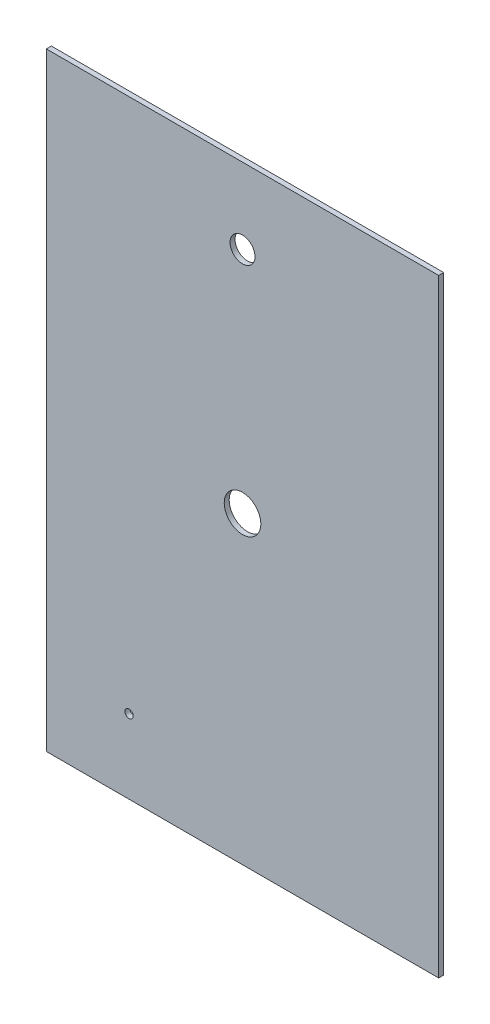
SolidWorks part; units mm, degrees
ref_plane "Alzado" through (0, 0, 0) normal (0, 0, 1) x (1, 0, 0)
ref_plane "Planta" through (0, 0, 0) normal (0, 1, 0) x (1, 0, 0)
ref_plane "Vista lateral" through (0, 0, 0) normal (1, 0, 0) x (0, 0, -1)
sketch "Sketch1" plane through (0, 0, 0) normal (0, 0, 1) x (1, 0, 0)
  line L1 (-118, 183) -> (118, 183)
  line L2 (-118, 183) -> (-118, -183)
  line L3 (-118, -183) -> (118, -183)
  line L4 (118, 183) -> (118, -183)
  line L5 (-118, 183) -> (118, -183) construction
  line L6 (-118, -183) -> (118, 183) construction
  point P0 (0, 0)
  dimension "D1" = 236
  dimension "D2" = 366
extrude "Boss-Extrude1" add sketch "Sketch1" along normal blind 3
sketch "Sketch2" plane through (0, 0, 0) normal (0, 0, -1) x (-1, 0, 0)
  circle A1 centre (0, 137.5) radius 7.5
  dimension "D1" = 15
extrude "Cut-Extrude2" cut sketch "Sketch2" against normal up to next
sketch "Sketch3" plane through (0, 0, 3) normal (0, 0, 1) x (1, 0, 0)
  circle A0 centre (0, 0) radius 11
  circle A1 centre (-58.75, -62.75) radius 10
  circle A2 centre (58.75, -62.75) radius 10
  circle A3 centre (0, 137.0156) radius 10
  dimension "D1" = 20
  dimension "D2" = 22
extrude "Cut-Extrude3" [suppressed] cut sketch "Sketch3" against normal up to next
sketch "Sketch4" plane through (0, 0, 0) normal (0, 0, 1) x (1, 0, 0)
  circle A0 centre (0, 0) radius 11
  circle A3 centre (0, 137.0156) radius 9
  dimension "D2" = 22
extrude "Cut-Extrude5" cut sketch "Sketch4" along normal up to next contours A0
sketch "Sketch5" plane through (0, 0, 0) normal (0, 0, -1) x (-1, 0, 0)
  circle A0 centre (68.2241, -138.4711) radius 2.5
  dimension "D1" = 5
extrude "Cut-Extrude7" cut sketch "Sketch5" against normal blind 5
sketch "Sketch6" [suppressed] plane through (0, 0, 0) normal (0, 0, -1) x (-1, 0, 0)
  circle A0 centre (78.6503, -117.3716) radius 2.5
  dimension "D1" = 5
extrude "Cut-Extrude8" [suppressed] cut sketch "Sketch6" against normal blind 5
